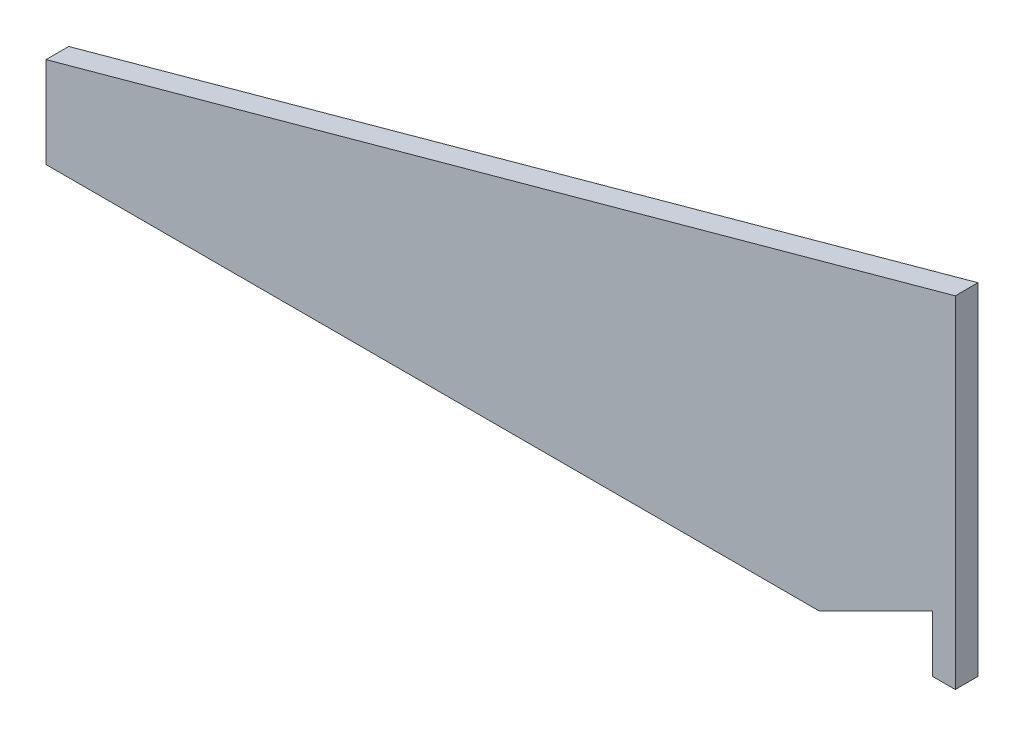
SolidWorks part; units mm, degrees
ref_plane "Front Plane" through (0, 0, 0) normal (0, 0, 1) x (1, 0, 0)
ref_plane "Top Plane" through (0, 0, 0) normal (0, 1, 0) x (1, 0, 0)
ref_plane "Right Plane" through (0, 0, 0) normal (1, 0, 0) x (0, 0, -1)
sketch "Sketch1" plane through (0, 0, 0) normal (0, 0, 1) x (1, 0, 0)
  line L0 (-31.5105, 0) -> (48.4895, 0)
  line L1 (-31.5105, 0) -> (-31.5105, 8)
  line L2 (-31.5105, 8) -> (48.4895, 30)
  line L3 (48.4895, 30) -> (48.4895, 0)
  line L4 (36.4895, 0) -> (46.4895, 5)
  line L5 (46.4895, 5) -> (46.4895, 0)
  dimension "D1" = 80
  dimension "D2" = 8
  dimension "D3" = 30
  dimension "D4" = 5
  dimension "D5" = 2
  dimension "D6" = 10
extrude "Boss-Extrude1" add sketch "Sketch1" along normal blind 2 contours L4 L5 L0 L3 L2 L1 region at (15.7582, 10.7101, 0)
